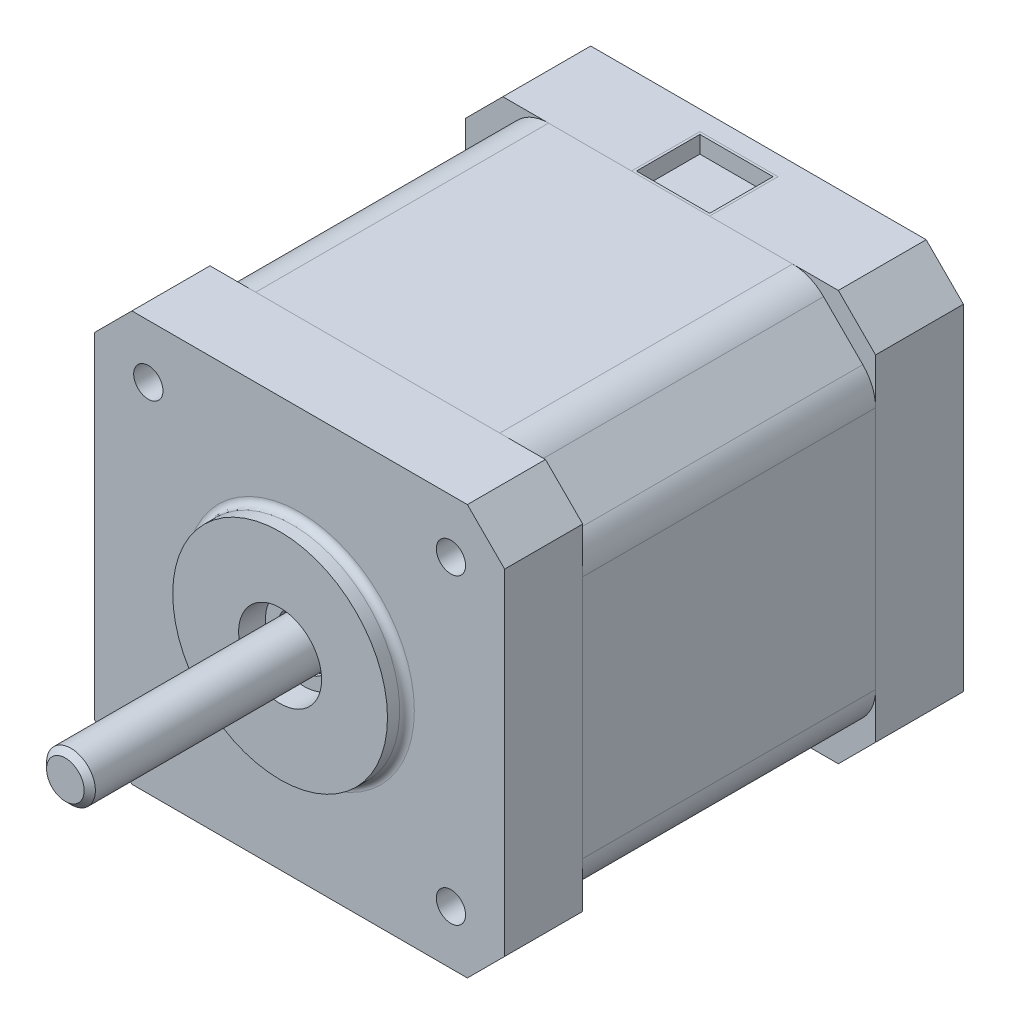
SolidWorks part; units mm, degrees
other "KABLO"
other "ÖN"
other "ORTA"
other "ARKA"
other "ŞAFT"
ref_plane "Front Plane" through (0, 0, 0) normal (0, 0, 1) x (1, 0, 0)
ref_plane "Top Plane" through (0, 0, 0) normal (0, 1, 0) x (1, 0, 0)
ref_plane "Right Plane" through (0, 0, 0) normal (1, 0, 0) x (0, 0, -1)
sketch "Sketch1" plane through (0, 0, 0) normal (0, 0, 1) x (1, 0, 0)
  line L0 (-15.5, 15.5) -> (15.5, 15.5) construction
  line L1 (17.1838, 21) -> (-17.1838, 21)
  line L2 (21, 17.1838) -> (21, -17.1838)
  line L3 (17.1838, -21) -> (-17.1838, -21)
  line L4 (-21, 17.1838) -> (-21, -17.1838)
  line L5 (19.0919, 19.0919) -> (-19.0919, -19.0919) construction
  line L6 (19.0919, -19.0919) -> (-19.0919, 19.0919) construction
  line L7 (15.5, 15.5) -> (15.5, -15.5) construction
  line L8 (15.5, -15.5) -> (-15.5, -15.5) construction
  line L9 (-15.5, -15.5) -> (-15.5, 15.5) construction
  line L10 (17.1838, 21) -> (21, 17.1838)
  line L11 (21, 17.1838) -> (21, 21) construction
  line L12 (21, 21) -> (17.1838, 21) construction
  line L13 (19.0919, 19.0919) -> (21, 21) construction
  line L14 (19.0919, 19.0919) -> (-19.0919, 19.0919) construction
  line L15 (-19.0919, 19.0919) -> (-19.0919, -19.0919) construction
  line L16 (-19.0919, -19.0919) -> (19.0919, -19.0919) construction
  line L17 (19.0919, -19.0919) -> (19.0919, 19.0919) construction
  line L18 (21, -17.1838) -> (17.1838, -21)
  line L19 (-17.1838, -21) -> (-21, -17.1838)
  line L20 (-21, 17.1838) -> (-17.1838, 21)
  line L21 (-19.0919, -19.0919) -> (-21, -21) construction
  line L22 (19.0919, -19.0919) -> (21, -21) construction
  line L23 (-19.0919, 19.0919) -> (-21, 21) construction
  line L24 (21, -17.1838) -> (21, -21) construction
  line L25 (21, -21) -> (17.1838, -21) construction
  line L26 (-17.1838, -21) -> (-21, -21) construction
  line L27 (-21, -21) -> (-21, -17.1838) construction
  line L28 (-21, 17.1838) -> (-21, 21) construction
  line L29 (-21, 21) -> (-17.1838, 21) construction
  circle A0 centre (-15.5, 15.5) radius 1.5 construction
  circle A1 centre (15.5, 15.5) radius 1.5 construction
  circle A2 centre (-15.5, -15.5) radius 1.5 construction
  circle A3 centre (15.5, -15.5) radius 1.5 construction
  point P0 (0, 0)
  dimension "D2" = 3
  dimension "D1" = 42
  dimension "D3" = 31
  dimension "D4" = 54
extrude "Boss-Extrude1" add sketch "Sketch1" against normal blind 8
sketch "Sketch3" plane through (0, 0, -8) normal (0, 0, -1) x (-1, 0, 0)
  line L0 (-19.6881, 15.6673) -> (-15.6673, 19.6881)
  line L1 (15.6673, 19.6881) -> (19.6881, 15.6673)
  line L2 (19.6881, -15.6673) -> (15.6673, -19.6881)
  line L3 (-15.6673, -19.6881) -> (-19.6881, -15.6673)
  line L4 (0, 0) -> (-17.6777, -17.6777) construction
  line L5 (0, 0) -> (17.6777, 17.6777) construction
  line L6 (-17.6777, 17.6777) -> (0, 0) construction
  line L7 (0, 0) -> (17.6777, -17.6777) construction
  line L8 (-17.1838, 21) -> (-21, 17.1838)
  line L9 (-21, 17.1838) -> (-21, -17.1838)
  line L10 (-21, -17.1838) -> (-17.1838, -21)
  line L11 (-17.1838, -21) -> (17.1838, -21)
  line L12 (17.1838, -21) -> (21, -17.1838)
  line L13 (21, -17.1838) -> (21, 17.1838)
  line L14 (21, 17.1838) -> (17.1838, 21)
  line L15 (17.1838, 21) -> (-17.1838, 21)
  line L16 (-17.6777, -17.6777) -> (-19.0919, -19.0919) construction
  line L17 (-21, 12.5) -> (-21, -12.5)
  line L18 (-17.1838, -21) -> (-21, -17.1838) construction
  line L19 (-12.5, -21) -> (12.5, -21)
  line L21 (21, -12.5) -> (21, 12.5)
  line L23 (12.5, 21) -> (-12.5, 21)
  arc A0 (-19.6881, -15.6673) -> (-21, -12.5) centre (-16.5208, -12.5) cw
  arc A1 (-15.6673, -19.6881) -> (-12.5, -21) centre (-12.5, -16.5208) ccw
  arc A2 (15.6673, -19.6881) -> (12.5, -21) centre (12.5, -16.5208) cw
  arc A3 (19.6881, -15.6673) -> (21, -12.5) centre (16.5208, -12.5) ccw
  arc A4 (19.6881, 15.6673) -> (21, 12.5) centre (16.5208, 12.5) cw
  arc A5 (15.6673, 19.6881) -> (12.5, 21) centre (12.5, 16.5208) ccw
  arc A6 (-15.6673, 19.6881) -> (-12.5, 21) centre (-12.5, 16.5208) cw
  arc A7 (-19.6881, 15.6673) -> (-21, 12.5) centre (-16.5208, 12.5) ccw
  dimension "D3" = 25
  dimension "D2" = 50
  dimension "D1" = 0
extrude "Boss-Extrude2" add sketch "Sketch3" along normal blind 30 separate body
sketch "Sketch4" plane through (0, 0, -38) normal (0, 0, -1) x (-1, 0, 0)
  line L8 (-17.1838, 21) -> (-21, 17.1838)
  line L9 (-21, 17.1838) -> (-21, -17.1838)
  line L10 (-21, -17.1838) -> (-17.1838, -21)
  line L11 (-17.1838, -21) -> (17.1838, -21)
  line L12 (17.1838, -21) -> (21, -17.1838)
  line L13 (21, -17.1838) -> (21, 17.1838)
  line L14 (21, 17.1838) -> (17.1838, 21)
  line L15 (17.1838, 21) -> (-17.1838, 21)
  line L16 (-17.1838, 21) -> (-21, 17.1838)
  line L17 (-21, 17.1838) -> (-21, -17.1838)
  line L18 (-21, -17.1838) -> (-17.1838, -21)
  line L19 (-17.1838, -21) -> (17.1838, -21)
  line L20 (17.1838, -21) -> (21, -17.1838)
  line L21 (21, -17.1838) -> (21, 17.1838)
  line L22 (21, 17.1838) -> (17.1838, 21)
  line L23 (17.1838, 21) -> (-17.1838, 21)
  dimension "D1" = 0
extrude "Boss-Extrude3" add sketch "Sketch4" along normal blind 9 separate body
sketch "Sketch5" plane through (0, 0, 0) normal (0, 0, 1) x (1, 0, 0)
  circle A0 centre (-15.5, 15.5) radius 1.5 construction
  circle A1 centre (15.5, 15.5) radius 1.5 construction
  circle A2 centre (15.5, -15.5) radius 1.5 construction
  circle A3 centre (-15.5, -15.5) radius 1.5 construction
  circle A4 centre (-15.5, 15.5) radius 1.5
  circle A5 centre (15.5, 15.5) radius 1.5
  circle A6 centre (15.5, -15.5) radius 1.5
  circle A7 centre (-15.5, -15.5) radius 1.5
extrude "Cut-Extrude1" cut sketch "Sketch5" against normal blind 4.5
sketch "Sketch6" plane through (0, 0, 0) normal (0, 0, 1) x (1, 0, 0)
  circle A0 centre (0, 0) radius 11
  dimension "D1" = 22
extrude "Boss-Extrude4" add sketch "Sketch6" along normal blind 2
sketch "Sketch9" plane through (0, 0, 2) normal (0, 0, 1) x (1, 0, 0)
  circle A0 centre (0, 0) radius 4.25
  dimension "D1" = 8.5
extrude "Cut-Extrude2" cut sketch "Sketch9" against normal blind 3
sketch "Sketch8" plane through (0, 0, -1) normal (0, 0, 1) x (1, 0, 0)
  circle A0 centre (0, 0) radius 2.5
  dimension "D1" = 5
extrude "Boss-Extrude5" add sketch "Sketch8" along normal blind 25 separate body
sketch "Sketch11" plane through (0, 0, -1) normal (0, 0, 1) x (1, 0, 0)
  circle A2 centre (0, 0) radius 4
  circle A3 centre (0, 0) radius 4.25 construction
  circle A4 centre (0, 0) radius 4.25 construction
  circle A5 centre (0, 0) radius 2.75
  dimension "D2" = 5.5
  dimension "D1" = 0.25
extrude "Boss-Extrude6" add sketch "Sketch11" along normal blind 0.5
fillet "Fillet1" radius 0.75 1 edges at (-11, 0, 0)
sketch "Sketch12" plane through (0, 0, 0) normal (1, 0, 0) x (0, 0, -1)
  line L0 (-24, 1.925) -> (-23.425, 2.5)
  line L1 (-24, 2.5) -> (-24, -2.5) construction
  line L2 (1, 2.5) -> (-24, 2.5) construction
  line L3 (-23.425, 2.5) -> (-23.425, 1.925) construction
  line L4 (-23.425, 1.925) -> (-24, 1.925) construction
  line L5 (-24, 1.925) -> (-24, 2.5)
  line L6 (-24, 2.5) -> (-23.425, 2.5)
  line L7 (-24, 0) -> (0, 0) construction
  dimension "D1" = 3.85
revolve "Cut-Revolve1" cut sketch "Sketch12" angle 360 about L7
sketch "Sketch13" plane through (0, 21, 0) normal (0, 1, 0) x (1, 0, 0)
  line L0 (0, 45) -> (0, 38) construction
  line L2 (-12.5, 38) -> (12.5, 38) construction
  line L3 (0, 45) -> (0, 47) construction
  line L4 (-4, 38) -> (4, 38)
  line L5 (-4, 38) -> (-4, 45)
  line L6 (-4, 45) -> (4, 45)
  line L7 (4, 38) -> (4, 45)
  line L8 (-17.1838, 47) -> (17.1838, 47) construction
  dimension "D1" = 2
  dimension "D2" = 8
extrude "Cut-Extrude3" cut sketch "Sketch13" against normal blind 2
sketch "Sketch14" plane through (0, 19, 0) normal (0, 1, 0) x (1, 0, 0)
  line L4 (-4, 45) -> (-4, 38)
  line L5 (-4, 38) -> (4, 38)
  line L6 (4, 38) -> (4, 45)
  line L7 (4, 45) -> (-4, 45)
  line L8 (-4, 45) -> (-4, 38)
  line L9 (-4, 38) -> (4, 38)
  line L10 (4, 38) -> (4, 45)
  line L11 (4, 45) -> (-4, 45)
  dimension "D1" = 0
extrude "Boss-Extrude7" add sketch "Sketch14" along normal blind 0.25 separate body
sketch "Sketch15" plane through (0, 19.25, 0) normal (0, 1, 0) x (1, 0, 0)
  line L0 (3.75, 38.25) -> (3.75, 44.75)
  line L1 (3.75, 44.75) -> (-3.75, 44.75)
  line L2 (-3.75, 44.75) -> (-3.75, 38.25)
  line L3 (-3.75, 38.25) -> (3.75, 38.25)
  line L4 (4, 45) -> (-4, 45)
  line L5 (-4, 45) -> (-4, 38)
  line L6 (-4, 38) -> (4, 38)
  line L7 (4, 38) -> (4, 45)
  line L8 (4, 45) -> (-4, 45)
  line L9 (-4, 45) -> (-4, 38)
  line L10 (-4, 38) -> (4, 38)
  line L11 (4, 38) -> (4, 45)
  dimension "D1" = 0
  dimension "D2" = 0.25
extrude "Boss-Extrude8" add sketch "Sketch15" along normal up to surface (1.75 mm away) up to face at (0, 21, -42)
